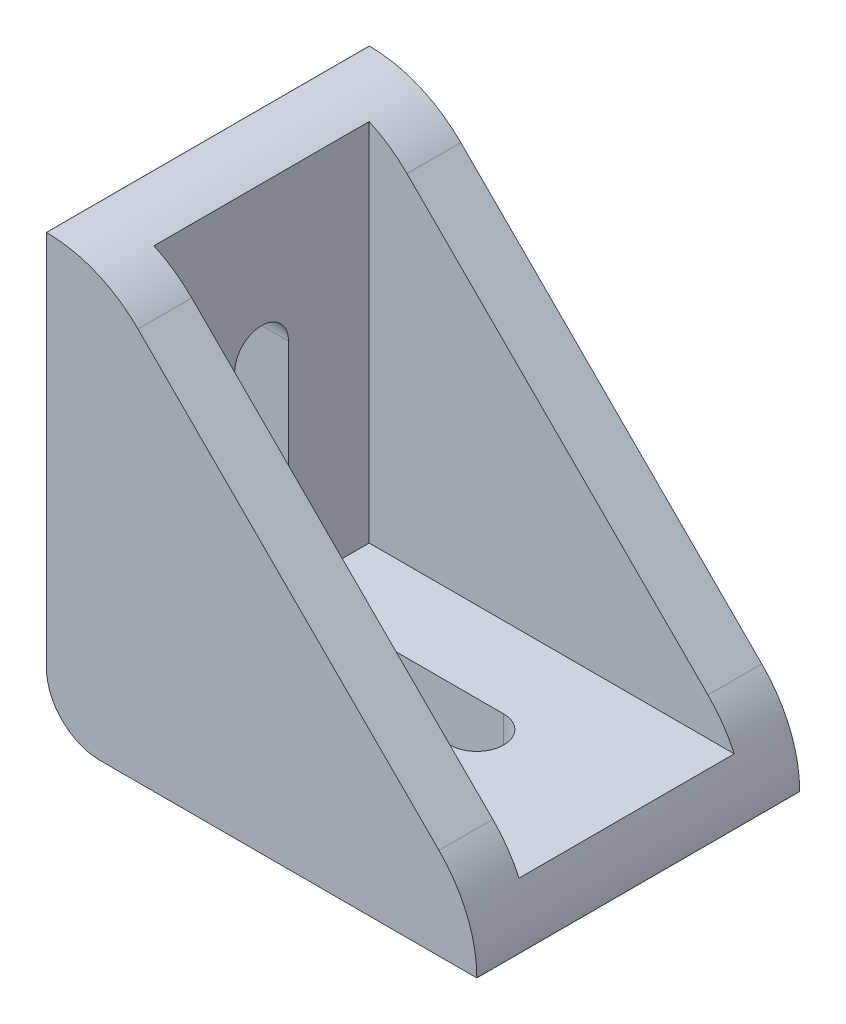
SolidWorks part; units mm, degrees
ref_plane "Front Plane" through (0, 0, 0) normal (0, 0, 1) x (1, 0, 0)
ref_plane "Top Plane" through (0, 0, 0) normal (0, 1, 0) x (1, 0, 0)
ref_plane "Right Plane" through (0, 0, 0) normal (1, 0, 0) x (0, 0, -1)
sketch "Sketch1" plane through (0, 0, 0) normal (0, 1, 0) x (1, 0, 0)
  line L1 (0, 0) -> (40, 0)
  line L2 (0, 0) -> (0, 30)
  line L3 (0, 30) -> (40, 30)
  line L4 (40, 0) -> (40, 30)
  dimension "D1" = 30
  dimension "D2" = 40
extrude "Boss-Extrude1" add sketch "Sketch1" along normal blind 5
sketch "Sketch2" plane through (0, 5, 0) normal (0, 1, 0) x (1, 0, 0)
  line L0 (0, 0) -> (40, 0) construction
  line L1 (0, 30) -> (5, 30)
  line L2 (0, 30) -> (0, 0)
  line L3 (0, 0) -> (5, 0)
  line L4 (5, 30) -> (5, 0)
  dimension "D1" = 5
extrude "Boss-Extrude2" add sketch "Sketch2" along normal blind 35
sketch "Sketch3" plane through (0, 0, 0) normal (0, 0, 1) x (1, 0, 0)
  line L0 (5, 40) -> (40, 5)
  line L1 (40, 5) -> (5, 5)
  line L2 (5, 5) -> (5, 40)
extrude "Boss-Extrude3" add sketch "Sketch3" against normal blind 5
sketch "Sketch4" plane through (0, 0, -30) normal (0, 0, -1) x (-1, 0, 0)
  line L0 (-40, 5) -> (-5, 40)
  line L1 (-5, 40) -> (-5, 5)
  line L2 (-5, 5) -> (-40, 5)
extrude "Boss-Extrude4" add sketch "Sketch4" against normal blind 5
sketch "Sketch5" plane through (0, 0, 0) normal (0, -1, 0) x (1, 0, 0)
  line L0 (0, -15) -> (40, -15) construction
  line L1 (0, -30) -> (0, 0) construction
  line L2 (40, 0) -> (40, -30) construction
  line L3 (20, -15) -> (20, 0) construction
  line L4 (0, 0) -> (40, 0) construction
  line L5 (15, 0) -> (15, -30) construction
  line L6 (40, -30) -> (0, -30) construction
  line L7 (25, 0) -> (25, -30) construction
  line L8 (15, -15) -> (25, -15) construction
  line L9 (15, -12.5) -> (25, -12.5)
  line L10 (15, -17.5) -> (25, -17.5)
  arc A0 (15, -12.5) -> (15, -17.5) centre (15, -15) ccw
  arc A1 (25, -17.5) -> (25, -12.5) centre (25, -15) ccw
  point P18 (20, -15)
  dimension "D1" = 5
  dimension "D2" = 5
  dimension "D3" = 5
extrude "Cut-Extrude1" cut sketch "Sketch5" against normal blind 5
sketch "Sketch6" plane through (0, 0, 0) normal (-1, 0, 0) x (0, 0, 1)
  line L0 (-15, 40) -> (-15, 0) construction
  line L1 (-30, 40) -> (0, 40) construction
  line L2 (-30, 0) -> (0, 0) construction
  line L3 (-30, 20) -> (0, 20) construction
  line L4 (-30, 40) -> (-30, 0) construction
  line L5 (0, 40) -> (0, 0) construction
  line L6 (-30, 25) -> (0, 25) construction
  line L7 (-30, 15) -> (0, 15) construction
  line L8 (-15, 25) -> (-15, 15) construction
  line L9 (-12.5, 25) -> (-12.5, 15)
  line L10 (-17.5, 25) -> (-17.5, 15)
  arc A0 (-12.5, 25) -> (-17.5, 25) centre (-15, 25) ccw
  arc A1 (-17.5, 15) -> (-12.5, 15) centre (-15, 15) ccw
  point P18 (-15, 20)
  dimension "D1" = 5
  dimension "D2" = 5
  dimension "D3" = 5
extrude "Cut-Extrude2" cut sketch "Sketch6" against normal blind 5
fillet "Fillet4" radius 12 3 edges at (40, 5, -2.5) (40, 5, -15) (40, 5, -27.5)
fillet "Fillet5" radius 12 3 edges at (5, 40, -2.5) (5, 40, -15) (5, 40, -27.5)
fillet "Fillet6" radius 5 1 edges at (0, 0, -15)
